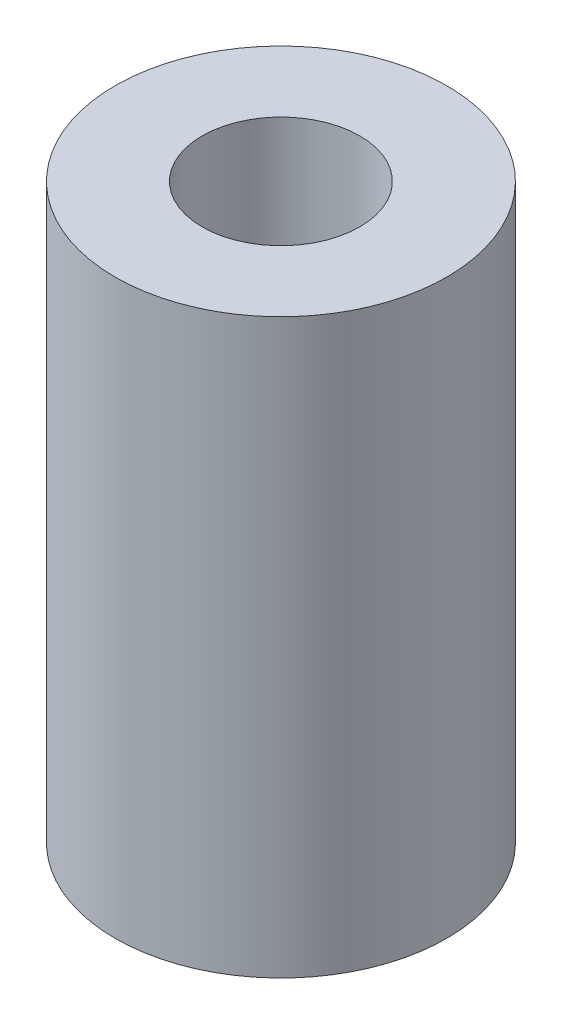
SolidWorks part; units mm, degrees
ref_plane "Front Plane" through (0, 0, 0) normal (0, 0, 1) x (1, 0, 0)
ref_plane "Top Plane" through (0, 0, 0) normal (0, 1, 0) x (1, 0, 0)
ref_plane "Right Plane" through (0, 0, 0) normal (1, 0, 0) x (0, 0, -1)
sketch "Sketch1" plane through (0, 0, 0) normal (0, 1, 0) x (1, 0, 0)
  circle A0 centre (0, 0) radius 5
  dimension "SLEEVE_OD" = 10
extrude "Boss-Extrude1" add sketch "Sketch1" along normal blind 17.2702
sketch "Sketch2" plane through (0, 0, 0) normal (0, 1, 0) x (1, 0, 0)
  circle A0 centre (0, 0) radius 2.3775
  dimension "BORE_D" = 4.7549
extrude "Cut-Extrude1" cut sketch "Sketch2" along normal through all
chamfer "Chamfer1" distance 0.7634 angle 69.31 rebuild error yes
